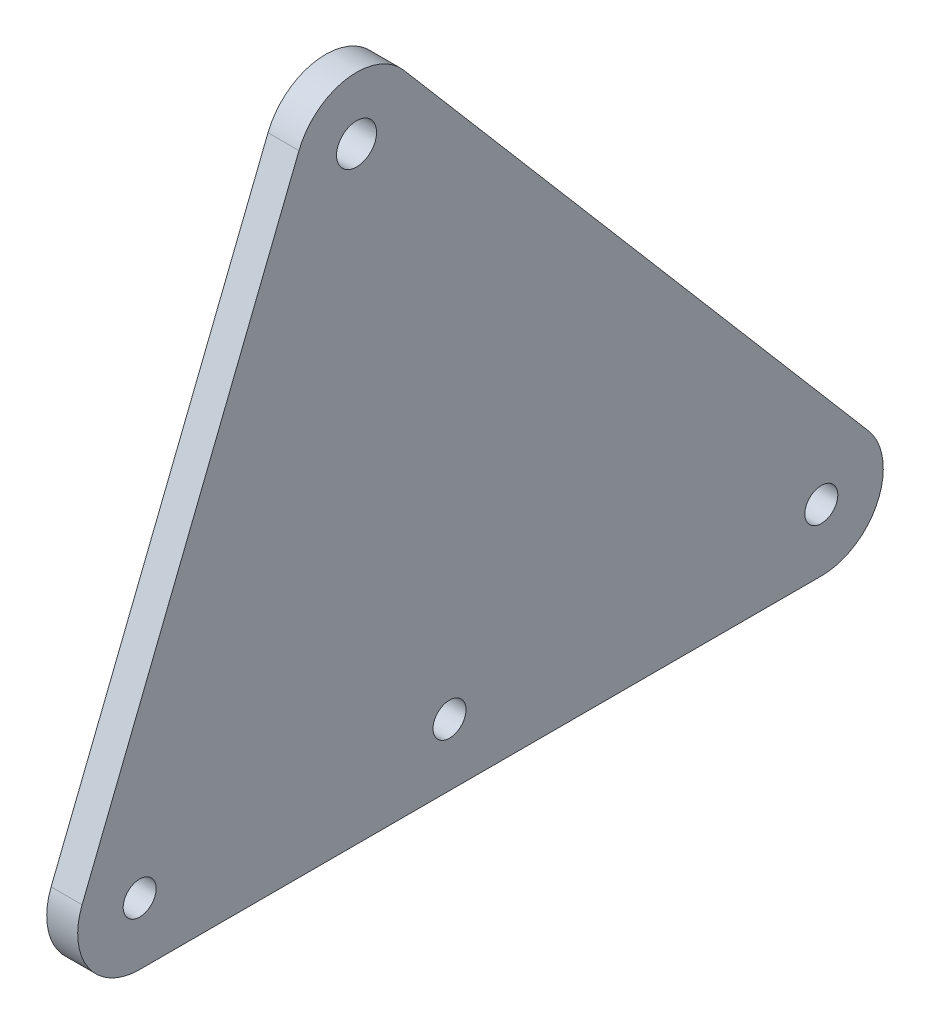
SolidWorks part; units mm, degrees
ref_plane "Front Plane" through (0, 0, 0) normal (0, 0, 1) x (1, 0, 0)
ref_plane "Top Plane" through (0, 0, 0) normal (0, 1, 0) x (1, 0, 0)
ref_plane "Right Plane" through (0, 0, 0) normal (1, 0, 0) x (0, 0, -1)
sketch "Sketch1" plane through (0, 0, 0) normal (1, 0, 0) x (0, 0, -1)
  line L0 (-56.249, -106.9349) -> (-11.799, 4.6981)
  line L1 (9.6612, 8.2433) -> (104.9112, -103.3897)
  line L2 (-44.45, -124.333) -> (95.25, -124.333)
  arc A0 (9.6612, 8.2433) -> (-11.799, 4.6981) centre (0, 0) ccw
  arc A1 (95.25, -124.333) -> (104.9112, -103.3897) centre (95.25, -111.633) ccw
  arc A2 (-56.249, -106.9349) -> (-44.45, -124.333) centre (-44.45, -111.633) ccw
  dimension "D1" = 139.7
  dimension "D2" = 111.633
  dimension "D3" = 44.45
  dimension "D4" = 25.4
extrude "Boss-Extrude1" add sketch "Sketch1" along normal blind 6.35 contours L1 A1 L2 A2 L0 A0
sketch "Sketch2" plane through (6.35, 0, 0) normal (1, 0, 0) x (0, 0, -1)
  circle A0 centre (-44.45, -111.633) radius 3.3782
  circle A1 centre (19.05, -111.633) radius 3.3782
  circle A2 centre (95.25, -111.633) radius 3.3782
  arc A3 (-56.249, -106.9349) -> (-44.45, -124.333) centre (-44.45, -111.633) ccw construction
  arc A4 (95.25, -124.333) -> (104.9112, -103.3897) centre (95.25, -111.633) ccw construction
  circle A5 centre (0, 0) radius 4.1021
  dimension "D2" = 0
  dimension "D3" = 0
  dimension "D4" = 63.5
  dimension "D5" = 6.7564
  dimension "D6" = 8.2042
extrude "Cut-Extrude1" cut sketch "Sketch2" against normal up to next
